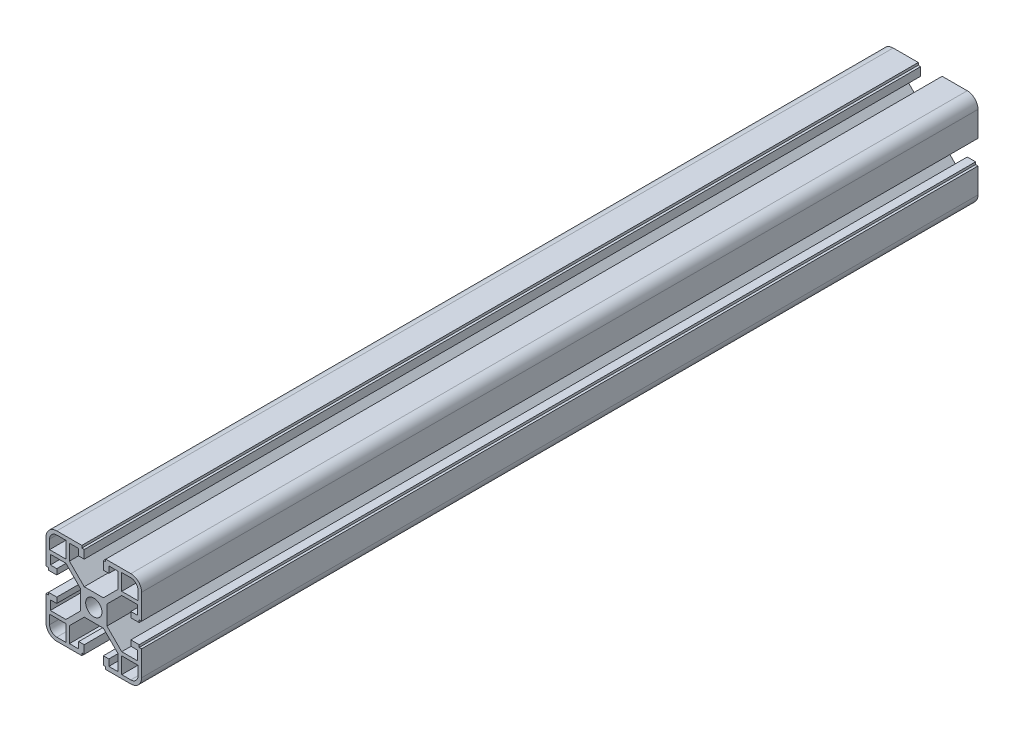
SolidWorks part; units mm, degrees
material "6061-T6 (SS)"
ref_plane "Front Plane" through (0, 0, 0) normal (0, 0, 1) x (1, 0, 0)
ref_plane "Top Plane" through (0, 0, 0) normal (0, 1, 0) x (1, 0, 0)
ref_plane "Right Plane" through (0, 0, 0) normal (1, 0, 0) x (0, 0, -1)
sketch "Sketch1" plane through (0, 0, 0) normal (0, 0, 1) x (1, 0, 0)
  line L0 (3.4, 0) -> (5.5, 0)
  line L1 (10.19, 11.69) -> (4, 5.5)
  line L2 (11.69, 10.19) -> (5.5, 4)
  line L3 (18.2, 10.19) -> (11.69, 10.19)
  line L4 (18.2, 10.19) -> (18.2, 6.3)
  line L5 (18.2, 6.3) -> (15.5, 6.3)
  line L6 (15.5, 6.3) -> (15.5, 4)
  line L7 (15.5, 4) -> (19, 4)
  line L8 (19, 4) -> (19, 5)
  line L9 (19, 5) -> (20, 5)
  line L10 (20, 5) -> (20, 15.5)
  line L11 (15.5, 20) -> (5, 20)
  line L12 (18.5, 11.69) -> (18.5, 15.5)
  line L13 (15.5, 18.5) -> (11.69, 18.5)
  line L14 (11.69, 11.69) -> (11.69, 18.5)
  line L15 (0, 3.4) -> (0, 5.5)
  line L16 (4, 5.5) -> (0, 5.5)
  line L17 (5, 20) -> (5, 19)
  line L18 (5.5, 0) -> (5.5, 4)
  line L19 (5, 19) -> (4, 19)
  line L20 (4, 19) -> (4, 15.5)
  line L21 (4, 15.5) -> (6.3, 15.5)
  line L22 (10.19, 11.69) -> (10.19, 18.2)
  line L23 (11.69, 11.69) -> (18.5, 11.69)
  line L24 (6.3, 18.2) -> (6.3, 15.5)
  line L25 (10.19, 18.2) -> (6.3, 18.2)
  arc A0 (20, 15.5) -> (15.5, 20) centre (15.5, 15.5) ccw
  arc A1 (18.5, 15.5) -> (15.5, 18.5) centre (15.5, 15.5) ccw
  arc A2 (3.4, 0) -> (0, 3.4) centre (0, 0) ccw
  point P4 (0, 4.45)
  dimension "D3" = 4.5
  dimension "D18" = 1.5
  dimension "D9" = 3.4
  dimension "D20" = 1.8
  dimension "D25" = 3
  dimension "D1" = 5.5
  dimension "D2" = 1.5
  dimension "D4" = 14.5
  dimension "D5" = 1.5
  dimension "D6" = 2.1
  dimension "D7" = 2.3
  dimension "D8" = 1.8
  dimension "D10" = 6.81
  dimension "D11" = 2.1
  dimension "D12" = 1
  dimension "D13" = 4.5
  dimension "D14" = 45
  dimension "D15" = 14.5
  dimension "D16" = 1
  dimension "D17" = 1.5
  dimension "D19" = 6.81
  dimension "D21" = 4.5
  dimension "D22" = 2.3
  dimension "D23" = 1
  dimension "D24" = 1
  dimension "D26" = 8.754
  dimension "D27" = 8.754
  dimension "D28" = 4
  dimension "D29" = 4
extrude "Boss-Extrude1" add sketch "Sketch1" along normal blind 350
mirror "Mirror1" about plane through (0, 0, 0) normal (0, 1, 0) of "Boss-Extrude1"
mirror "Mirror2" about plane through (0, 0, 0) normal (1, 0, 0) of "Boss-Extrude1"
mirror "Mirror3" about plane through (0, 0, 0) normal (0, 1, 0) of "Mirror2"
